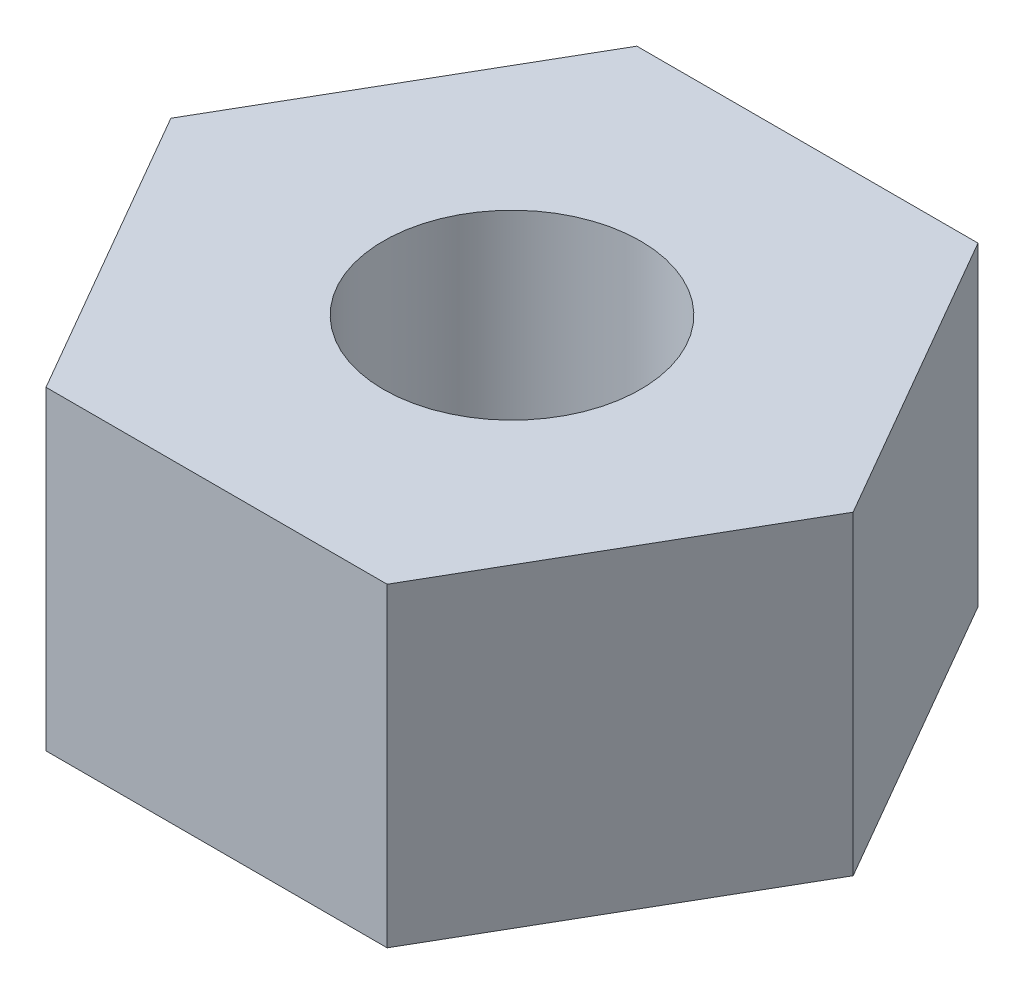
SolidWorks part; units mm, degrees
ref_plane "Front Plane" through (0, 0, 0) normal (0, 0, 1) x (1, 0, 0)
ref_plane "Top Plane" through (0, 0, 0) normal (0, 1, 0) x (1, 0, 0)
ref_plane "Right Plane" through (0, 0, 0) normal (1, 0, 0) x (0, 0, -1)
sketch "Sketch1" plane through (0, 0, 0) normal (0, 1, 0) x (1, 0, 0)
  line L1 (6.5, 0) -> (3.25, 5.6292)
  line L2 (3.25, 5.6292) -> (-3.25, 5.6292)
  line L3 (-3.25, 5.6292) -> (-6.5, 0)
  line L4 (-6.5, 0) -> (-3.25, -5.6292)
  line L5 (-3.25, -5.6292) -> (3.25, -5.6292)
  line L6 (3.25, -5.6292) -> (6.5, 0)
  circle A0 centre (0, 0) radius 6.5
  circle A1 centre (0, 0) radius 2.45
  circle A2 centre (0, 0) radius 5.6292 construction
  dimension "D1" = 13
  dimension "D2" = 4.9
  dimension "D3" = 13
extrude "Boss-Extrude1" add sketch "Sketch1" along normal blind 6 contours L5 L6 L1 L2 L3 L4 A1 region at (4.7261, 0, 2.7286)
